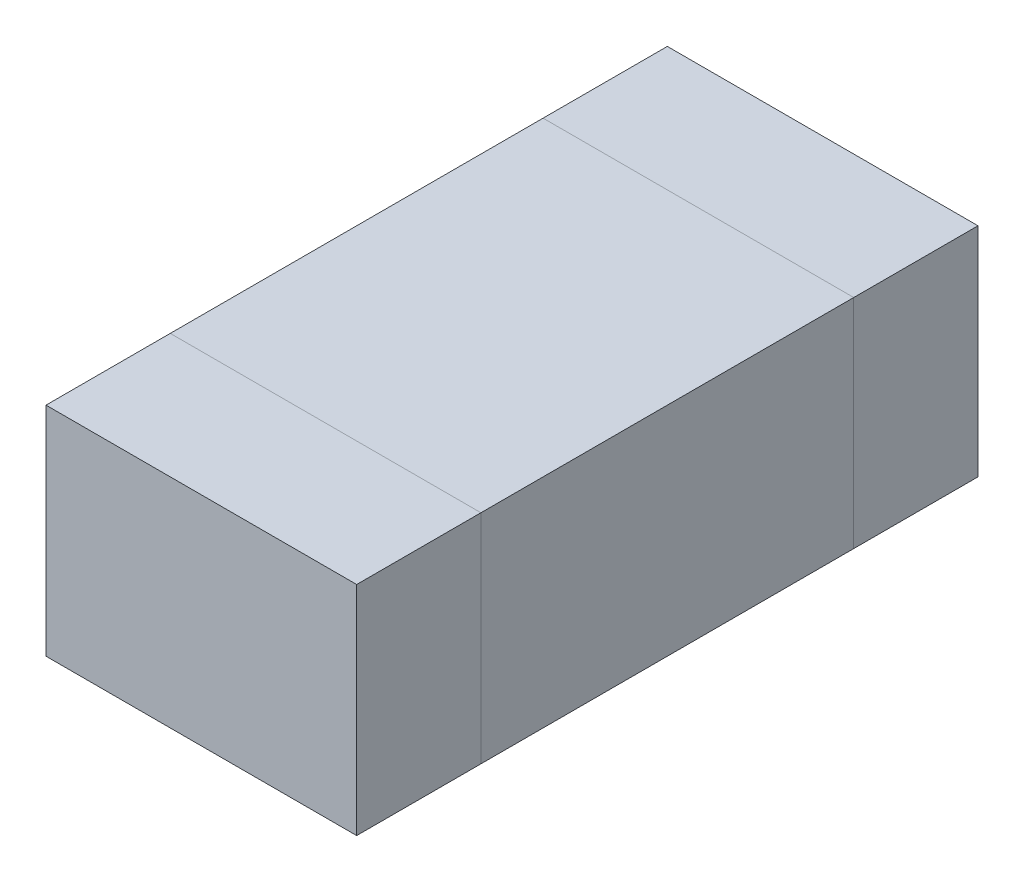
SolidWorks part; units mm, degrees
ref_plane "Front Plane" through (0, 0, 0) normal (0, 0, 1) x (1, 0, 0)
ref_plane "Top Plane" through (0, 0, 0) normal (0, 1, 0) x (1, 0, 0)
ref_plane "Right Plane" through (0, 0, 0) normal (1, 0, 0) x (0, 0, -1)
sketch "MainBodyS" plane through (0, 0, 0) normal (0, 1, 0) x (1, 0, 0)
  line L1 (-0.25, 0.3) -> (0.25, 0.3)
  line L2 (-0.25, 0.3) -> (-0.25, -0.3)
  line L3 (-0.25, -0.3) -> (0.25, -0.3)
  line L4 (0.25, 0.3) -> (0.25, -0.3)
  line L5 (-0.25, 0.3) -> (0.25, -0.3) construction
  line L6 (-0.25, -0.3) -> (0.25, 0.3) construction
  point P0 (0, 0)
  dimension "Length" = 0.6
  dimension "Width" = 0.5
extrude "MainBody" add sketch "MainBodyS" along normal blind 0.35
sketch "LeftBodyS" plane through (0, 0, 0) normal (0, -1, 0) x (-1, 0, 0)
  line L1 (0.25, -0.3) -> (-0.25, -0.3)
  line L2 (0.25, -0.3) -> (0.25, -0.5)
  line L3 (0.25, -0.5) -> (-0.25, -0.5)
  line L4 (-0.25, -0.3) -> (-0.25, -0.5)
  dimension "SolderLength" = 0.2
extrude "LeftBody" add sketch "LeftBodyS" against normal up to surface (0.35 mm away) separate body up to face at (0, 0.35, 0)
sketch "RightBodyS" plane through (0, 0, 0) normal (0, -1, 0) x (1, 0, 0)
  line L0 (0.25, 0.3) -> (0.25, 0.5) construction
  line L1 (-0.25, -0.3) -> (0.25, -0.3)
  line L2 (-0.25, -0.3) -> (-0.25, -0.5)
  line L3 (-0.25, -0.5) -> (0.25, -0.5)
  line L4 (0.25, -0.3) -> (0.25, -0.5)
extrude "RightBody" add sketch "RightBodyS" against normal up to surface (0.35 mm away) separate body up to face at (0, 0.35, 0)
